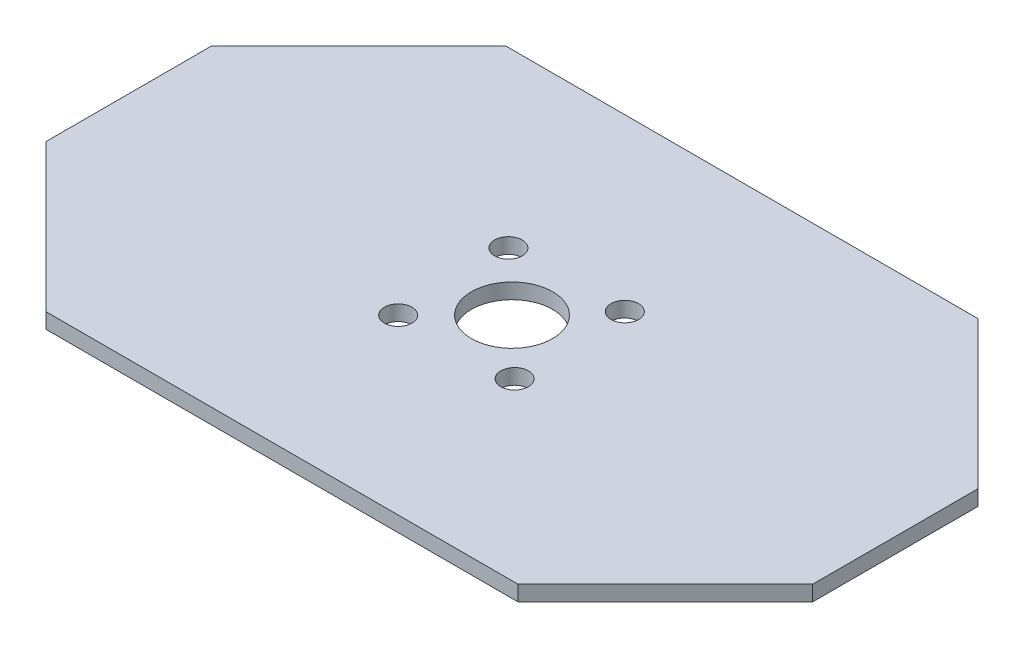
SolidWorks part; units mm, degrees
ref_plane "Alzado" through (0, 0, 0) normal (0, 0, 1) x (1, 0, 0)
ref_plane "Planta" through (0, 0, 0) normal (0, 1, 0) x (1, 0, 0)
ref_plane "Vista lateral" through (0, 0, 0) normal (1, 0, 0) x (0, 0, -1)
sketch "Croquis1" plane through (0, 0, 0) normal (0, 1, 0) x (1, 0, 0)
  line L0 (-50, 10.7839) -> (-30.7839, 30)
  line L1 (-30.7839, 30) -> (30.7839, 30)
  line L2 (-50, 10.7839) -> (-50, -10.7839)
  line L3 (-30.7839, -30) -> (30.7839, -30)
  line L4 (50, 10.7839) -> (50, -10.7839)
  line L5 (-50, 30) -> (50, -30) construction
  line L6 (-50, -30) -> (50, 30) construction
  line L7 (30.7839, 30) -> (50, 10.7839)
  line L8 (50, -10.7839) -> (30.7839, -30)
  line L9 (-50, -10.7839) -> (-30.7839, -30)
  line L10 (-50, 30) -> (-30.7839, 30) construction
  line L11 (-50, 30) -> (-50, 10.7839) construction
  line L12 (30.7839, 30) -> (50, 30) construction
  line L13 (50, 30) -> (50, 10.7839) construction
  line L14 (50, -10.7839) -> (50, -30) construction
  line L15 (50, -30) -> (30.7839, -30) construction
  line L16 (-30.7839, -30) -> (-50, -30) construction
  line L17 (-50, -30) -> (-50, -10.7839) construction
  line L18 (50, 0) -> (-50, 0) construction
  line L19 (0, -30) -> (0, 30) construction
  line L20 (30.7839, -30) -> (30.7839, 30) construction
  line L21 (-30.7839, -30) -> (-30.7839, 30) construction
  point P0 (0, 0)
  dimension "D1" = 60
  dimension "D2" = 100
  dimension "D3" = 45
extrude "Saliente-Extruir1" add sketch "Croquis1" along normal blind 2
sketch "Croquis2" plane through (0, 2, 0) normal (0, 1, 0) x (1, 0, 0)
  line L0 (50, 0) -> (-50, 0) construction
  line L1 (50, -10.7839) -> (50, 10.7839) construction
  line L2 (-50, 10.7839) -> (-50, -10.7839) construction
  line L3 (0, 30) -> (0, -30) construction
  line L4 (30.7839, 30) -> (-30.7839, 30) construction
  line L5 (-30.7839, -30) -> (30.7839, -30) construction
  line L6 (0, 0) -> (-7.4246, -7.4246) construction
  circle A0 centre (0, 0) radius 5.3
  circle A1 centre (0, 0) radius 10.5 construction
  circle A2 centre (-7.4246, -7.4246) radius 1.8
  circle A3 centre (-7.8277, 7.3574) radius 1.8
  circle A4 centre (6.9543, 7.7605) radius 1.8
  circle A5 centre (7.3574, -7.0215) radius 1.8
  point P26 (-0.2352, 0.168)
  dimension "D1" = 10.6
  dimension "D2" = 21
  dimension "D3" = 3.6
  dimension "D4" = 45
  dimension "D5" = 4
extrude "Cortar-Extruir1" cut sketch "Croquis2" against normal up to next
